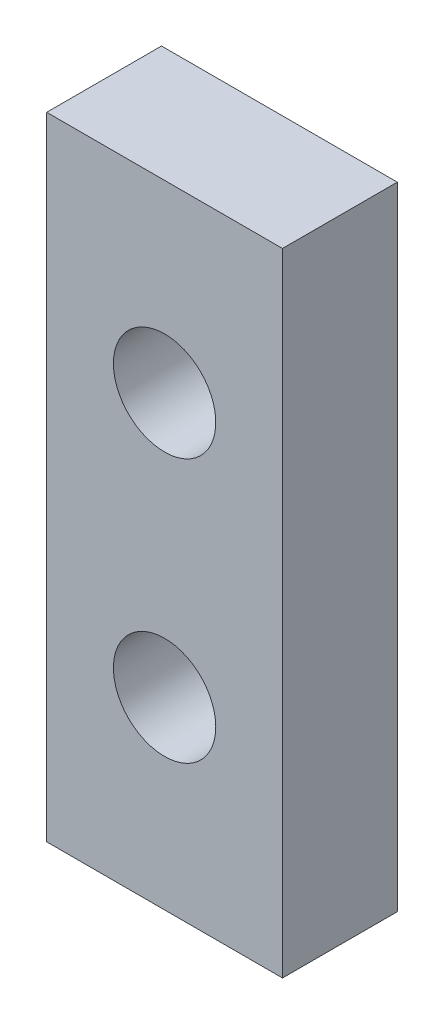
SolidWorks part; units mm, degrees
material "Maple"
ref_plane "Front Plane" through (0, 0, 0) normal (0, 0, 1) x (1, 0, 0)
ref_plane "Top Plane" through (0, 0, 0) normal (0, 1, 0) x (1, 0, 0)
ref_plane "Right Plane" through (0, 0, 0) normal (1, 0, 0) x (0, 0, -1)
sketch "Sketch2" plane through (0, 0, 0) normal (0, 0, 1) x (1, 0, 0)
  line L1 (-3.26, 8.735) -> (3.26, 8.735)
  line L2 (-3.26, 8.735) -> (-3.26, -8.735)
  line L3 (-3.26, -8.735) -> (3.26, -8.735)
  line L4 (3.26, 8.735) -> (3.26, -8.735)
  line L5 (-3.26, 8.735) -> (3.26, -8.735) construction
  line L6 (-3.26, -8.735) -> (3.26, 8.735) construction
  point P0 (0, 0)
  dimension "D1" = 6.52
  dimension "D2" = 17.47
extrude "Boss-Extrude1" add sketch "Sketch2" along normal blind 3.175
sketch "Sketch3" plane through (0, 0, 3.175) normal (0, 0, 1) x (1, 0, 0)
  line L0 (0, -8.735) -> (0, -3.645) construction
  line L1 (-3.26, -8.735) -> (3.26, -8.735) construction
  line L2 (0, 0) -> (2.3769, 0) construction
  line L3 (3.26, -8.735) -> (3.26, 8.735) construction
  circle A0 centre (0, -3.645) radius 1.415
  circle A1 centre (0, 3.645) radius 1.415
  dimension "D2" = 2.83
  dimension "D1" = 5.09
extrude "Cut-Extrude1" cut sketch "Sketch3" against normal through all
sketch "Sketch4" plane through (0, 0, 3.175) normal (0, 0, 1) x (1, 0, 0)
  line L0 (0, -43.4708) -> (0, 43.4708) construction
  point P4 (0, 0)
ref_axis "Axis1" through (0, 43.4708, 3.175) along (0, -1, 0)
equation "\"kerf\"= 0.17 / 2"
equation "\"D1@Sketch2\"= 6.35mm + 2*\"kerf\""
equation "\"D2@Sketch2\"= 17.30mm + 2*\"kerf\""
equation "\"D2@Sketch3\"=3.00mm - 2*\"kerf\""
